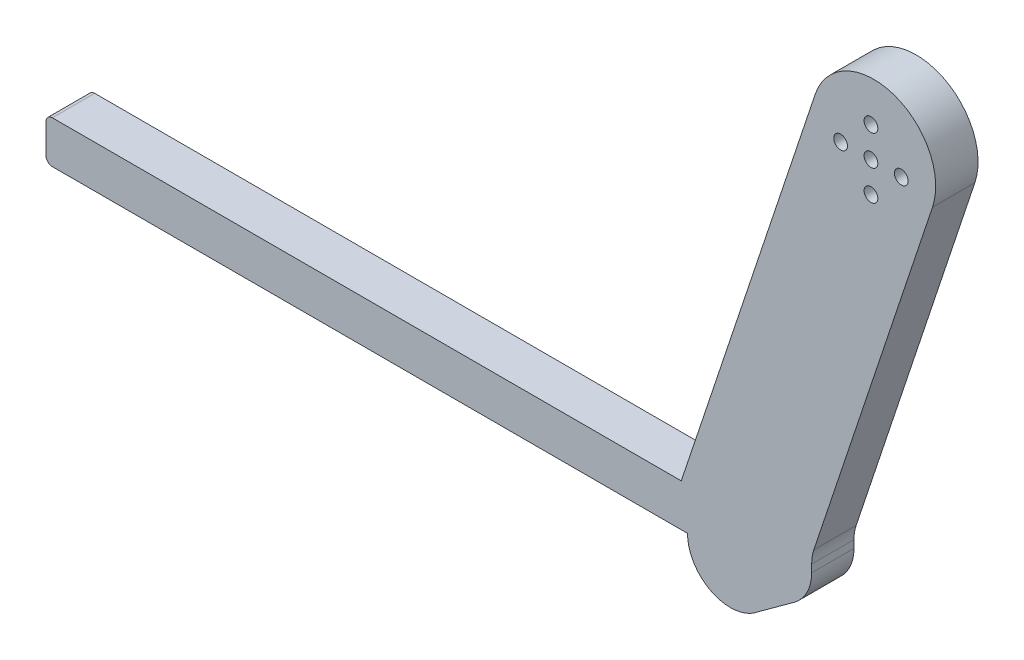
SolidWorks part; units mm, degrees
ref_plane "前视基准面" through (0, 0, 0) normal (0, 0, 1) x (1, 0, 0)
ref_plane "上视基准面" through (0, 0, 0) normal (0, 1, 0) x (1, 0, 0)
ref_plane "右视基准面" through (0, 0, 0) normal (1, 0, 0) x (0, 0, -1)
sketch "草图1" plane through (0, 0, 0) normal (0, 0, 1) x (1, 0, 0)
  line L4 (-150, -1.5) -> (-150, -8.5)
  line L5 (-148.5, -10) -> (1.474, -10)
  line L6 (30.7849, -3.4108) -> (30.7849, -1.6228)
  line L7 (0, 0) -> (31.6228, 94.8683)
  line L8 (31.298, 1.5395) -> (59.3292, 85.6329)
  line L9 (-148.5, 0) -> (0, 0)
  line L12 (18.1803, -17.6764) -> (26.6706, -11.4953)
  arc A1 (-150, -8.5) -> (-148.5, -10) centre (-148.5, -8.5) ccw
  arc A2 (-148.5, 0) -> (-150, -1.5) centre (-148.5, -1.5) ccw
  circle A3 centre (44.7875, 88.1014) radius 1.62
  circle A6 centre (51.9465, 88.1014) radius 1.62
  circle A7 centre (44.7875, 95.2604) radius 1.62
  circle A8 centre (44.7875, 80.9424) radius 1.62
  circle A9 centre (37.6285, 88.1014) radius 1.62
  circle A10 centre (44.7875, 88.1014) radius 9.8
  arc A13 (31.6228, 94.8683) -> (59.3292, 85.6329) centre (45.476, 90.2506) cw
  arc A14 (1.474, -10) -> (18.1803, -17.6764) centre (11.5908, -10) ccw
  arc A15 (30.7849, -3.4108) -> (26.6706, -11.4953) centre (20.7849, -3.4108) cw
  arc A16 (31.298, 1.5395) -> (30.7849, -1.6228) centre (40.7849, -1.6228) ccw
  point P26 (0, 0)
  point P31 (0, -10)
  dimension "D1" = 10
  dimension "D2" = 10
extrude "凸台-拉伸1" add sketch "草图1" along normal blind 10 contours L9 L7 A13 L8 A16 L6 A15 L12 A14 L5 A1 L4 A2
extrude "切除-拉伸2" cut sketch "草图1<15>" along normal blind 10 contours A9 | A7 | A3 | A6 | A8
sketch "草图1<15>" plane through (0, 0, 0) normal (0, 0, 1) x (1, 0, 0) same geometry as "草图1"
extrude "切除-拉伸3" cut sketch "草图1<16>" along normal blind 2.2 contours A10
sketch "草图1<16>" plane through (0, 0, 0) normal (0, 0, 1) x (1, 0, 0) same geometry as "草图1"
